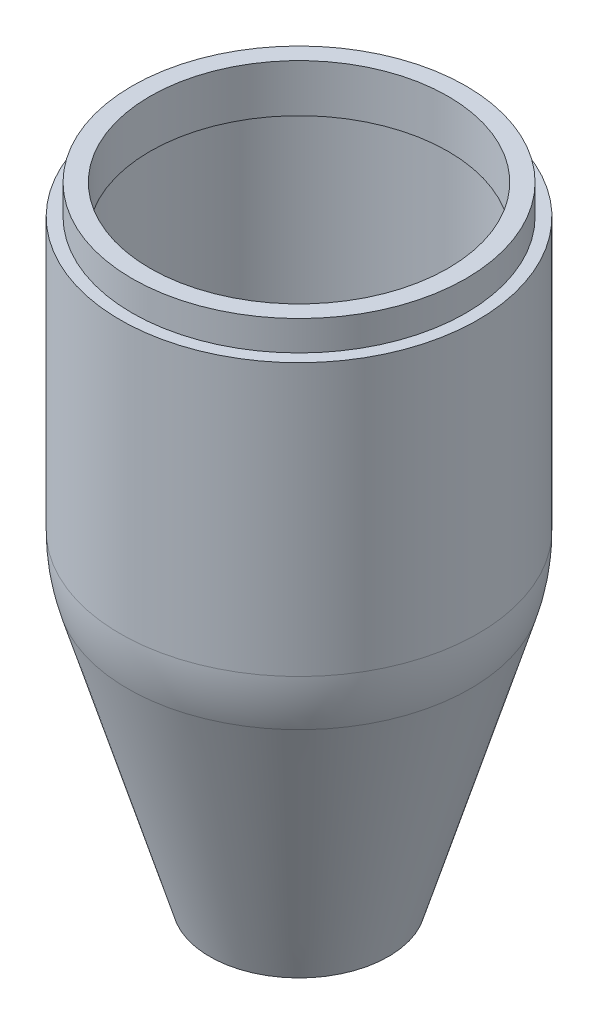
SolidWorks part; units mm, degrees
ref_plane "Front Plane" through (0, 0, 0) normal (0, 0, 1) x (1, 0, 0)
ref_plane "Top Plane" through (0, 0, 0) normal (0, 1, 0) x (1, 0, 0)
ref_plane "Right Plane" through (0, 0, 0) normal (1, 0, 0) x (0, 0, -1)
sketch "Sketch1" plane through (0, 0, 0) normal (0, 0, 1) x (1, 0, 0)
  line L0 (0, 0) -> (0, 100)
  line L4 (0, 0) -> (15, 0)
  line L5 (0, 100) -> (30, 100)
  line L6 (30, 100) -> (30, 54.4031)
  line L7 (28.7348, 45.7826) -> (15, 0)
  arc A0 (30, 54.4031) -> (28.7348, 45.7826) centre (0, 54.4031) cw
  dimension "D1" = 30
revolve "Revolve1" add sketch "Sketch1" angle 360 about L0
sketch "Sketch4" plane through (0, 100, 0) normal (0, 1, 0) x (1, 0, 0)
  circle A2 centre (0, 0) radius 28
  circle A3 centre (0, 0) radius 28
  dimension "D1" = 2
extrude "Extrude-Thin2" add sketch "Sketch4" along normal blind 5 thin thin type one direction reverse wall 3
shell "Shell1" thickness 3 removed face at (0, 100, 25)
sketch "Sketch5" plane through (0, 0, 0) normal (0, 0, 1) x (1, 0, 0)
  line L0 (0, 84.1873) -> (7.7856, 84.1873)
  line L1 (0, 76.4017) -> (7.7856, 76.4017)
  arc A0 (7.7856, 84.1873) -> (7.7856, 76.4017) centre (7.7856, 80.2945) cw
